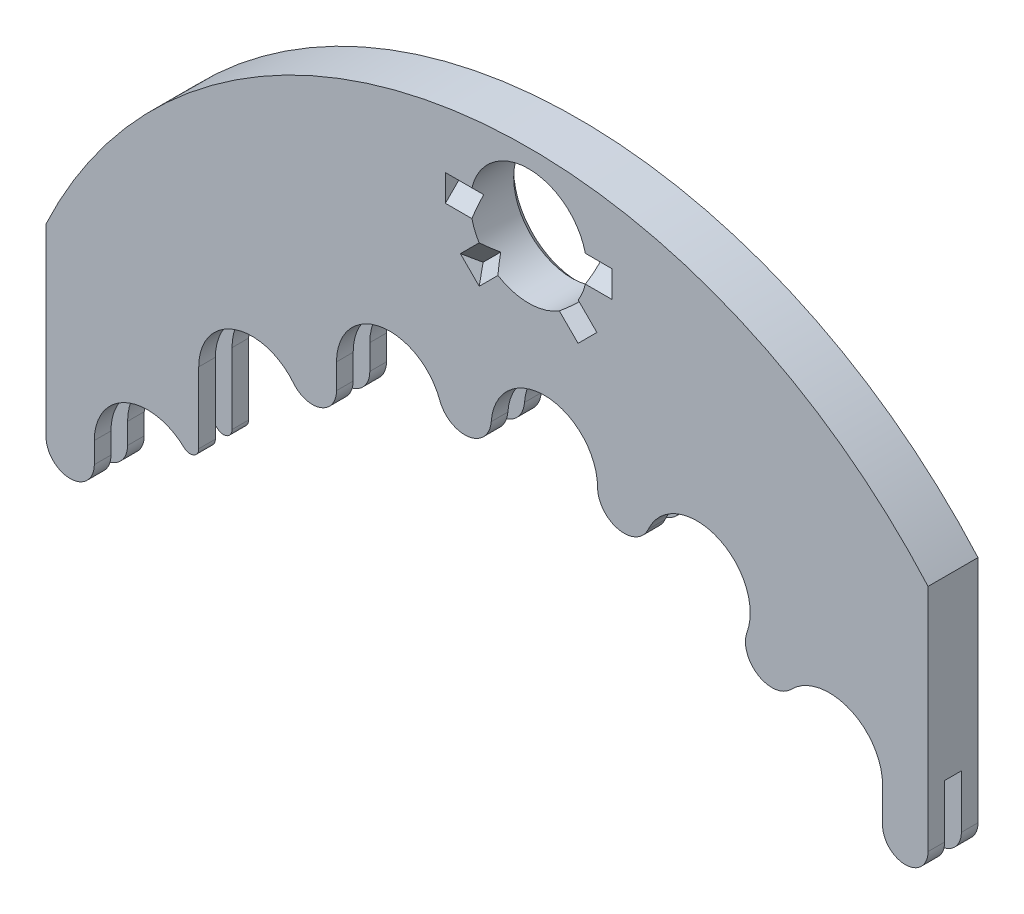
SolidWorks part; units mm, degrees
ref_plane "Front Plane" through (0, 0, 0) normal (0, 0, 1) x (1, 0, 0)
ref_plane "Top Plane" through (0, 0, 0) normal (0, 1, 0) x (1, 0, 0)
ref_plane "Right Plane" through (0, 0, 0) normal (1, 0, 0) x (0, 0, -1)
sketch "Sketch1" plane through (0, 0, 0) normal (0, 0, 1) x (1, 0, 0)
  line L1 (-13.25, -7.75) -> (13.25, -7.75)
  line L2 (-13.25, -7.75) -> (-13.25, 7.75)
  line L3 (-13.25, 7.75) -> (13.25, 7.75)
  line L4 (13.25, -7.75) -> (13.25, 7.75)
  line L5 (-13.25, -7.75) -> (13.25, 7.75) construction
  line L6 (-13.25, 7.75) -> (13.25, -7.75) construction
  point P0 (0, 0)
  dimension "D1" = 26.5
  dimension "D2" = 15.5
extrude "Boss-Extrude1" add sketch "Sketch1" along normal mid plane 1.5
sketch "Sketch2" plane through (0, 0, 0.75) normal (0, 0, 1) x (1, 0, 0)
  line L0 (-13.25, 9.75) -> (-13.25, -1.4861)
  line L3 (-13.25, 7.75) -> (-13.25, -7.75) construction
  line L4 (13.25, 7.75) -> (-13.25, 7.75) construction
  line L5 (13.25, -7.75) -> (13.25, 7.75) construction
  line L7 (13.25, 2.333) -> (13.25, 9.75)
  line L8 (13.25, 9.75) -> (-13.25, 9.75)
  line L9 (13.25, 9.75) -> (-13.25, 9.75)
  arc A0 (13.25, 2.333) -> (-13.25, -1.4861) centre (1.25, -8.25) ccw
  dimension "D1" = 14.5
  dimension "D2" = 32
  dimension "D3" = 2
extrude "Cut-Extrude1" cut sketch "Sketch2" against normal up to next (1.5 mm away)
sketch "Sketch3" plane through (0, 0, 0) normal (0, 0, 1) x (1, 0, 0)
  line L0 (-13.25, -1.4861) -> (-13.25, -7.75) construction
  circle A0 centre (1.25, -13.55) radius 16
  arc A1 (13.25, 2.333) -> (-13.25, -1.4861) centre (1.25, -8.25) ccw construction
  dimension "D1" = 32
  dimension "D3" = 21.3
  dimension "D2" = 14.5
extrude "Cut-Extrude2" cut sketch "Sketch3" against normal mid plane 0.5
sketch "Sketch5" plane through (0, 0, 0.75) normal (0, 0, 1) x (1, 0, 0)
  line L0 (13.25, -7.75) -> (13.25, 2.333) construction
  circle A0 centre (1.25, -13.55) radius 13
  arc A1 (13.25, -2.967) -> (-13.25, -6.7861) centre (1.25, -13.55) ccw construction
  dimension "D1" = 26
extrude "Cut-Extrude3" cut sketch "Sketch5" against normal through all
sketch "Sketch11" plane through (0, 0, 0.75) normal (0, 0, 1) x (1, 0, 0)
  line L0 (13.25, -7.75) -> (13.25, 2.333) construction
  line L1 (11.2555, -5.25) -> (13.25, -5.25)
  line L5 (12.8844, -7.75) -> (13.25, -7.75) construction
  line L6 (13.25, -7.75) -> (13.25, -5.25)
  line L7 (12.8844, -7.75) -> (13.25, -7.75)
  arc A0 (13.25, 2.333) -> (-13.25, -1.4861) centre (1.25, -8.25) ccw construction
  arc A1 (12.8844, -7.75) -> (-10.3844, -7.75) centre (1.25, -13.55) ccw construction
  arc A2 (12.8844, -7.75) -> (11.2555, -5.25) centre (1.25, -13.55) ccw
  dimension "D1" = 13
extrude "Cut-Extrude9" cut sketch "Sketch11" against normal through all
sketch "Sketch8" plane through (0, 0, 0.75) normal (0, 0, 1) x (1, 0, 0)
  line L0 (1.25, -13.55) -> (1.25, 9.3677) construction
  circle A0 centre (1.25, 5.45) radius 1.75
  arc A4 (13.25, 2.333) -> (-13.25, -1.4861) centre (1.25, -8.25) ccw construction
  dimension "D1" = 2.3
  dimension "D2" = 3.5
extrude "Cut-Extrude6" cut sketch "Sketch8" against normal through all
sketch "Sketch4" plane through (0, 0, 0) normal (0, 0, 1) x (1, 0, 0)
  line L0 (1.25, -13.55) -> (1.25, -0.05) construction
  line L1 (1.25, -13.55) -> (1.7211, -0.0582) construction
  line L2 (1.25, -13.55) -> (6.3072, -1.033) construction
  line L3 (1.25, -13.55) -> (10.2833, -3.5175) construction
  line L4 (1.25, -13.55) -> (-2.9217, -0.7107) construction
  line L5 (1.25, -13.55) -> (-7.0614, -2.9119) construction
  line L6 (1.25, -13.55) -> (-10.1986, -6.3961) construction
  circle A0 centre (1.25, -13.55) radius 13 construction
  arc A1 (13.25, -2.967) -> (-13.25, -6.7861) centre (1.25, -13.55) ccw construction
  circle A2 centre (1.25, -13.55) radius 13.5 construction
  circle A3 centre (1.7211, -0.0582) radius 1.6
  circle A4 centre (6.3072, -1.033) radius 1.6
  circle A5 centre (10.2833, -3.5175) radius 1.6
  circle A6 centre (-2.9217, -0.7107) radius 1.6
  circle A7 centre (-7.0614, -2.9119) radius 1.6
  circle A8 centre (-10.1986, -6.3961) radius 1.6
  dimension "D1" = 26
  dimension "D6" = 3.2
  dimension "D7" = 18
  dimension "D3" = 2
  dimension "D4" = 22
  dimension "D5" = 42
  dimension "D8" = 38
  dimension "D9" = 58
  dimension "D2" = 0.5
extrude "Cut-Extrude7" cut sketch "Sketch4" against normal through all both and the other way through all
sketch "Sketch9" plane through (0, 0, 0.75) normal (0, 0, 1) x (1, 0, 0)
  line L0 (-11.7986, -6.3961) -> (-11.7986, -7.0243)
  line L1 (-13.25, -1.4861) -> (-13.25, -7.75) construction
  line L2 (-13.25, -7.75) -> (-11.0512, -7.75) construction
  line L3 (-13.25, -7.0243) -> (-13.25, -8.25)
  line L5 (-11.0512, -7.75) -> (-11.0512, -8.25)
  line L6 (-13.25, -8.25) -> (-11.0512, -8.25)
  line L7 (-13.25, -8.25) -> (-11.0512, -8.25)
  arc A0 (-8.913, -5.4436) -> (-11.0512, -7.75) centre (-10.1986, -6.3961) ccw construction
  arc A1 (-11.7986, -6.3961) -> (-11.0512, -7.75) centre (-10.1986, -6.3961) ccw
  arc A2 (-13.25, -7.0243) -> (-11.7986, -7.0243) centre (-12.5243, -7.0243) ccw
  dimension "D1" = 0.5
extrude "Cut-Extrude8" cut sketch "Sketch9" against normal through all
sketch "Sketch12" plane through (0, 0, 0.75) normal (0, 0, 1) x (1, 0, 0)
  line L0 (11.8833, -3.5175) -> (11.8833, -4.5666)
  line L1 (13.25, -5.25) -> (11.2555, -5.25) construction
  line L2 (13.25, -5.25) -> (13.25, 2.333) construction
  line L4 (13.25, -5.75) -> (13.25, -4.5666)
  line L5 (13.25, -5.75) -> (11.2555, -5.75)
  line L6 (11.2555, -5.25) -> (11.2555, -5.75)
  arc A0 (10.998, -4.949) -> (8.7849, -2.9564) centre (10.2833, -3.5175) ccw construction
  arc A1 (11.8833, -4.5666) -> (13.25, -4.5666) centre (12.5666, -4.5666) ccw
  arc A2 (11.2555, -5.25) -> (10.998, -4.949) centre (1.25, -13.55) ccw construction
  arc A3 (10.998, -4.949) -> (11.8833, -3.5175) centre (10.2833, -3.5175) ccw
  arc A4 (11.2555, -5.25) -> (10.998, -4.949) centre (1.25, -13.55) ccw
  dimension "D1" = 0.5
extrude "Cut-Extrude10" cut sketch "Sketch12" against normal through all contours L5 L6 A4 A3 L0 A1 L4
sketch "Sketch13" plane through (0, 0, 0.75) normal (0, 0, 1) x (1, 0, 0)
  line L0 (-8.6614, -2.9119) -> (-8.6614, -5.0428)
  line L1 (-4.5217, -0.7107) -> (-4.5217, -1.4604)
  line L2 (11.8833, -3.5175) -> (11.8833, -4.5666) construction
  line L3 (11.8833, -3.5175) -> (11.8833, -6.9786)
  arc A0 (7.8117, -1.5776) -> (9.1343, -2.4041) centre (8.5616, -1.849) ccw
  arc A1 (7.4684, -2.1337) -> (4.7073, -1.0181) centre (6.3072, -1.033) ccw construction
  arc A2 (11.8833, -3.5175) -> (8.7849, -2.9564) centre (10.2833, -3.5175) ccw construction
  arc A3 (8.7849, -2.9564) -> (7.4684, -2.1337) centre (1.25, -13.55) ccw construction
  arc A4 (3.1888, -0.6954) -> (0.2126, -0.5915) centre (1.7211, -0.0582) ccw construction
  arc A5 (-1.3247, -0.8075) -> (-4.1569, -1.7278) centre (-2.9217, -0.7107) ccw construction
  arc A6 (-5.5276, -2.4566) -> (-7.8743, -4.29) centre (-7.0614, -2.9119) ccw construction
  arc A7 (-8.913, -5.4436) -> (-11.7986, -6.3961) centre (-10.1986, -6.3961) ccw construction
  arc A8 (11.8833, -3.5175) -> (9.1343, -2.4041) centre (10.2833, -3.5175) ccw
  arc A9 (7.8117, -1.5776) -> (4.8467, -0.3797) centre (6.3072, -1.033) ccw
  arc A10 (3.3211, -0.0554) -> (0.1252, 0.0562) centre (1.7211, -0.0582) ccw
  arc A11 (-1.4192, -0.1608) -> (-4.5217, -0.7107) centre (-2.9217, -0.7107) ccw
  arc A12 (-5.8117, -1.9127) -> (-8.6614, -2.9119) centre (-7.0614, -2.9119) ccw
  arc A13 (-8.6655, -5.9386) -> (-9.1007, -5.2323) centre (-10.1986, -6.3961) ccw
  arc A16 (3.3211, -0.0554) -> (4.8467, -0.3797) centre (4.1187, -0.054) ccw
  arc A17 (4.5743, -1.5001) -> (3.1142, -1.1898) centre (1.25, -13.55) ccw
  arc A18 (11.8833, -6.9786) -> (-8.6655, -5.9386) centre (1.25, -13.55) ccw
  arc A19 (4.7073, -1.0181) -> (3.1888, -0.6954) centre (1.25, -13.55) ccw construction
  arc A20 (-1.4192, -0.1608) -> (0.1252, 0.0562) centre (-0.6702, 0.1133) ccw
  arc A21 (0.2126, -0.5915) -> (-1.3247, -0.8075) centre (1.25, -13.55) ccw construction
  arc A22 (-9.1007, -5.2323) -> (-8.6614, -5.0428) centre (-8.9219, -5.0428) ccw
  arc A24 (-7.8743, -4.29) -> (-8.913, -5.4436) centre (1.25, -13.55) ccw construction
  arc A26 (-5.8117, -1.9127) -> (-4.5217, -1.4604) centre (-5.246, -1.4604) ccw
  arc A27 (-4.1569, -1.7278) -> (-5.5276, -2.4566) centre (1.25, -13.55) ccw construction
  dimension "D1" = 0.5
extrude "Cut-Extrude11" cut sketch "Sketch13" against normal through all
chamfer "Chamfer1" distance 0.2 angle 45 1 edges at (3, 5.45, -0.75)
ref_plane "Plane1" through (1.25, 0, 0) normal (-1, 0, 0) x (0, 0, 1)
sketch "Sketch14" plane through (1.25, 0, 0) normal (-1, 0, 0) x (0, 0, 1)
  line L0 (-0.55, 5.45) -> (1.3969, 5.45) construction
  line L1 (-0.55, 7.2) -> (-0.55, 3.7) construction
  line L2 (0.75, 5.85) -> (0.35, 5.45)
  line L3 (0.75, -1.4861) -> (0.75, 7.75) construction
  line L4 (0.35, 5.45) -> (0.75, 5.05)
  line L5 (0.75, 5.05) -> (0.75, 5.85)
  dimension "D1" = 0.4
extrude "Cut-Extrude12" cut sketch "Sketch14" along normal blind 2.5 contours L2 L4 L5
pattern_circular "CirPattern1" count 2 over 45 about axis through (1.25, 5.45, -0.75) along (0, 0, 1) of "Cut-Extrude12"
mirror "Mirror1" about plane through (1.25, 0, 0) normal (-1, 0, 0) of "CirPattern1"
